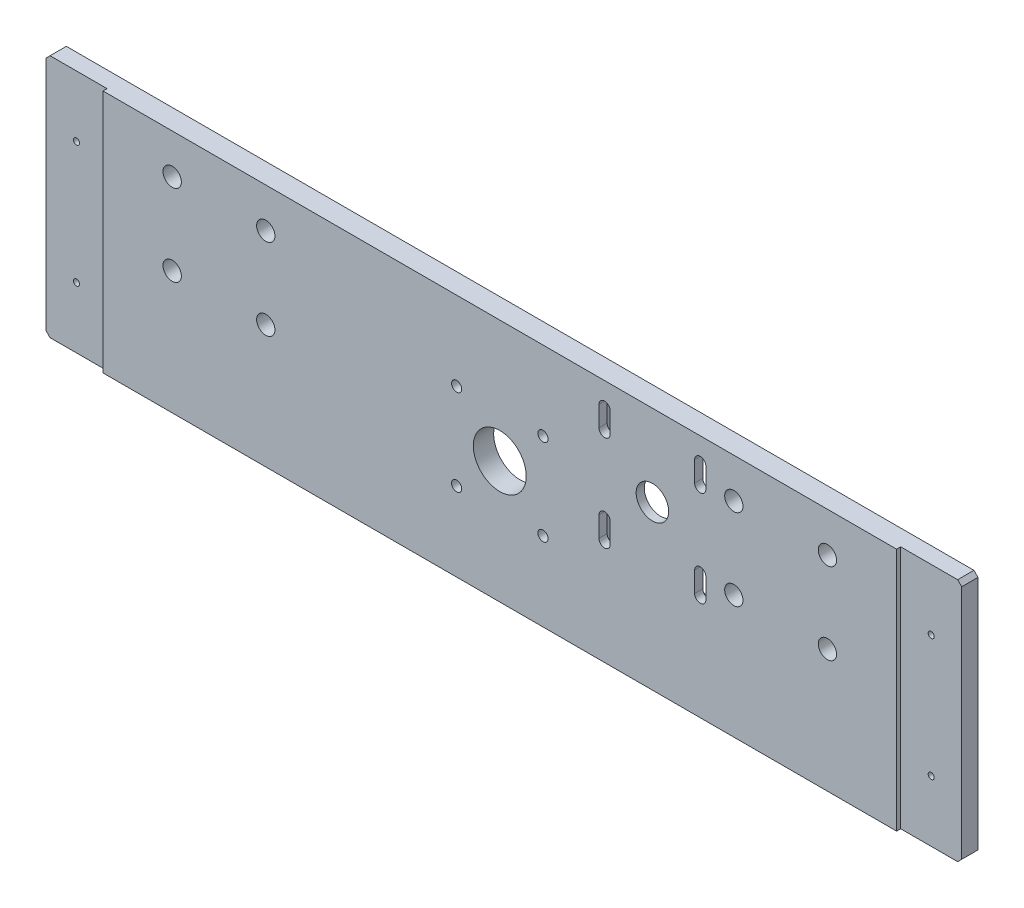
SolidWorks part; units mm, degrees
ref_plane "Piano frontale" through (0, 0, 0) normal (0, 0, 1) x (1, 0, 0)
ref_plane "Piano superiore" through (0, 0, 0) normal (0, 1, 0) x (1, 0, 0)
ref_plane "Piano destro" through (0, 0, 0) normal (1, 0, 0) x (0, 0, -1)
sketch "Schizzo1" plane through (0, 0, 0) normal (0, 0, 1) x (1, 0, 0)
  line L0 (225, 120) -> (225, 0) construction
  line L1 (2, 0) -> (448, 0)
  line L2 (0, 2) -> (0, 118)
  line L3 (2, 120) -> (448, 120)
  line L4 (450, 2) -> (450, 118)
  line L7 (225, 60) -> (243.5099, 60) construction
  line L9 (225, 60) -> (194.6932, 90.3068) construction
  line L21 (0, 118) -> (2, 120)
  line L22 (2, 0) -> (0, 2)
  line L23 (448, 0) -> (450, 2)
  line L24 (448, 120) -> (450, 118)
  line L25 (225, 60) -> (450, 60) construction
  line L26 (344.754, 80) -> (282.8483, 80) construction
  line L27 (323.5, 108.5) -> (323.5, 98.5) construction
  line L28 (320.75, 108.5) -> (320.75, 98.5)
  line L29 (326.25, 108.5) -> (326.25, 98.5)
  line L30 (276.5, 108.5) -> (276.5, 98.5) construction
  line L31 (279.25, 108.5) -> (279.25, 98.5)
  line L32 (273.75, 108.5) -> (273.75, 98.5)
  line L33 (323.5, 51.5) -> (323.5, 61.5) construction
  line L34 (320.75, 51.5) -> (320.75, 61.5)
  line L35 (326.25, 51.5) -> (326.25, 61.5)
  line L36 (276.5, 51.5) -> (276.5, 61.5) construction
  line L37 (279.25, 51.5) -> (279.25, 61.5)
  line L38 (273.75, 51.5) -> (273.75, 61.5)
  line L42 (300, 120) -> (300, 0) construction
  circle A0 centre (225, 60) radius 13
  circle A1 centre (225, 60) radius 30 construction
  circle A2 centre (246.2132, 81.2132) radius 2.5
  circle A3 centre (386, 100.5) radius 4.5
  circle A4 centre (246.2132, 38.7868) radius 2.5
  circle A5 centre (203.7868, 38.7868) radius 2.5
  circle A6 centre (110, 100.5) radius 4.5
  circle A7 centre (110, 60.5) radius 4.5
  circle A8 centre (64, 60.5) radius 4.5
  circle A9 centre (64, 100.5) radius 4.5
  circle A10 centre (386, 60.5) radius 4.5
  circle A11 centre (15, 30) radius 1.5
  circle A12 centre (435, 30) radius 1.5
  circle A13 centre (203.7868, 81.2132) radius 2.5
  circle A14 centre (340, 60.5) radius 4.5
  circle A15 centre (340, 100.5) radius 4.5
  circle A17 centre (435, 90) radius 1.5
  circle A18 centre (15, 90) radius 1.5
  arc A19 (320.75, 108.5) -> (326.25, 108.5) centre (323.5, 108.5) cw
  arc A20 (326.25, 98.5) -> (320.75, 98.5) centre (323.5, 98.5) cw
  arc A21 (279.25, 108.5) -> (273.75, 108.5) centre (276.5, 108.5) ccw
  arc A22 (273.75, 98.5) -> (279.25, 98.5) centre (276.5, 98.5) ccw
  arc A23 (320.75, 51.5) -> (326.25, 51.5) centre (323.5, 51.5) ccw
  arc A24 (326.25, 61.5) -> (320.75, 61.5) centre (323.5, 61.5) ccw
  arc A25 (279.25, 51.5) -> (273.75, 51.5) centre (276.5, 51.5) cw
  arc A26 (273.75, 61.5) -> (279.25, 61.5) centre (276.5, 61.5) cw
  circle A27 centre (300, 80) radius 8
  point P0 (0, 0)
  point P1 (450, 120)
  point P2 (0, 120)
  point P3 (450, 0)
  point P9 (203.7868, 81.2132)
  point P13 (203.7868, 81.2132)
  point P80 (300, 80)
  point P83 (323.5, 103.5)
  point P90 (276.5, 103.5)
  point P97 (323.5, 56.5)
  point P104 (276.5, 56.5)
  dimension "D4" = 26
  dimension "D15" = 3
  dimension "D17" = 5
  dimension "D25" = 16
  dimension "D8" = 45
  dimension "D1" = 120
  dimension "D2" = 450
  dimension "D3" = 60
  dimension "D14" = 30
  dimension "D16" = 15
  dimension "D18" = 40
  dimension "D23" = 23.5
  dimension "D24" = 23.5
  dimension "D26" = 5.5
  dimension "D27" = 10
  dimension "D29" = 150
extrude "Estrusione-Estrusione1" add sketch "Schizzo1" against normal blind 10
sketch "Schizzo2" plane through (0, 0, 0) normal (0, 0, 1) x (1, 0, 0)
  line L0 (448, 120) -> (2, 120) construction
  line L1 (30, 120) -> (0, 120)
  line L2 (30, 120) -> (30, 0)
  line L3 (30, 0) -> (0, 0)
  line L4 (0, 120) -> (0, 0)
  line L5 (225, 120) -> (225, 0) construction
  line L6 (630.4389, 120) -> (630.4389, 0)
  line L7 (600.4389, 0) -> (630.4389, 0)
  line L8 (600.4389, 120) -> (600.4389, 0)
  line L9 (600.4389, 120) -> (630.4389, 120)
  line L10 (2, 0) -> (448, 0) construction
  line L11 (450, 120) -> (450, 0)
  line L12 (420, 0) -> (450, 0)
  line L13 (420, 120) -> (420, 0)
  line L14 (420, 120) -> (450, 120)
  dimension "D1" = 30
extrude "Taglio-Estrusione1" cut sketch "Schizzo2" against normal blind 2
sketch "Schizzo3" plane through (0, 0, -10) normal (0, 0, -1) x (-1, 0, 0)
  line L0 (-300, 80) -> (-300, 120) construction
  line L2 (-300, 80) -> (-346.4615, 80) construction
  line L4 (-270, 44) -> (-330, 44)
  line L5 (-270, 44) -> (-270, 116)
  line L6 (-270, 116) -> (-330, 116)
  line L7 (-330, 44) -> (-330, 116)
  line L8 (-270, 44) -> (-330, 116) construction
  line L9 (-270, 116) -> (-330, 44) construction
  dimension "D1" = 60
  dimension "D2" = 72
extrude "Taglio-Estrusione2" cut sketch "Schizzo3" against normal blind 6
